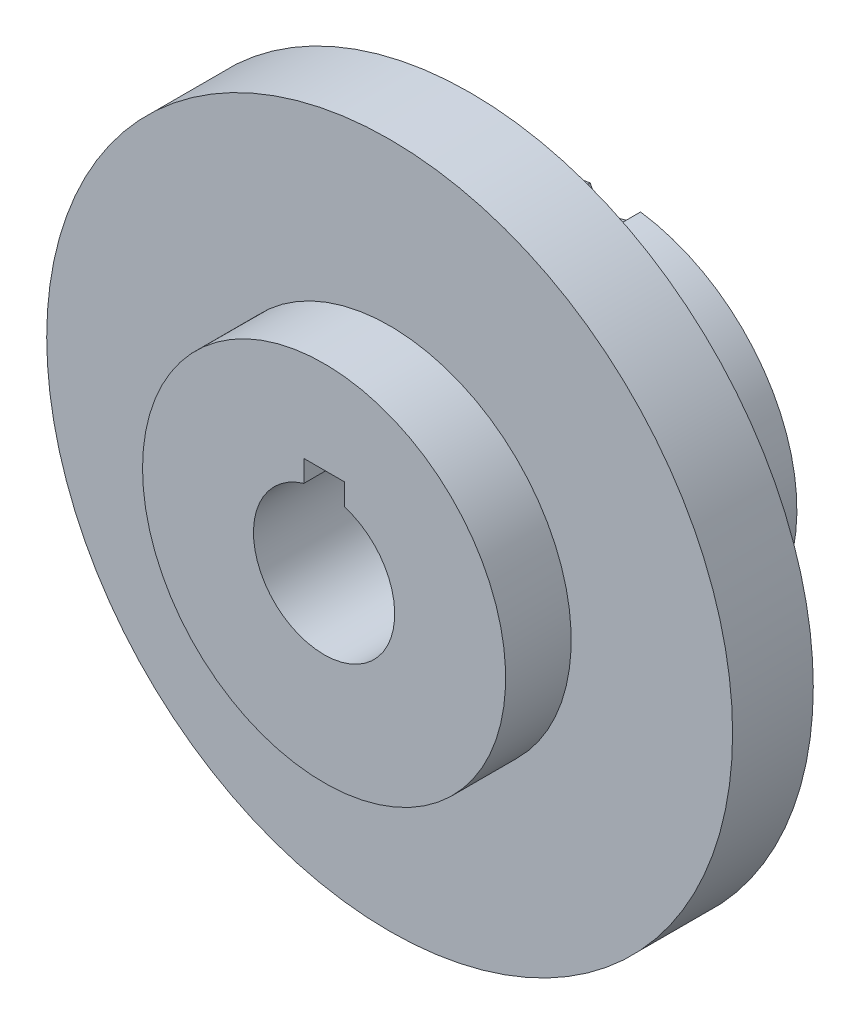
SolidWorks part; units mm, degrees
ref_plane "Спереди" through (0, 0, 0) normal (0, 0, 1) x (1, 0, 0)
ref_plane "Сверху" through (0, 0, 0) normal (0, 1, 0) x (1, 0, 0)
ref_plane "Справа" through (0, 0, 0) normal (1, 0, 0) x (0, 0, -1)
sketch "Эскиз1" plane through (0, 0, 0) normal (0, 0, 1) x (1, 0, 0)
  line L1 (-2, 8.85) -> (2, 8.85)
  line L2 (-2, 8.85) -> (-2, 6.7082)
  line L4 (2, 8.85) -> (2, 6.7082)
  arc A0 (-2, 6.7082) -> (2, 6.7082) centre (0, 0) ccw
  arc A1 (-2.5, 17.8255) -> (-16.6874, -6.7477) centre (0, 0) ccw
  arc A2 (-2.5, 17.8255) -> (2.5, 17.8255) centre (0, 18.9352) ccw
  arc A3 (-16.6874, -6.7477) -> (-14.1874, -11.0778) centre (-16.3984, -9.4676) cw
  arc A4 (14.1874, -11.0778) -> (16.6874, -6.7477) centre (16.3984, -9.4676) cw
  arc A5 (-14.1874, -11.0778) -> (14.1874, -11.0778) centre (0, 0) ccw
  arc A6 (16.6874, -6.7477) -> (2.5, 17.8255) centre (0, 0) ccw
  dimension "D1" = 14
  dimension "D2" = 36
  dimension "D4" = 2.7352
  dimension "D5" = 2.7352
  dimension "D6" = 2.7352
  dimension "D18" = 18
  dimension "D3" = 2
  dimension "D7" = 2
  dimension "D8" = 2.5
  dimension "D9" = 14.1874
  dimension "D10" = 16.3984
  dimension "D11" = 2.5
  dimension "D12" = 14.1874
  dimension "D13" = 16.3984
  dimension "D14" = 8.85
  dimension "D15" = 8.85
  dimension "D16" = 2
  dimension "D17" = 2
extrude "Вытянуть1" add sketch "Эскиз1" along normal up to surface (14.3746 mm away) from offset 6 offset against normal yes
sketch "Эскиз3" plane through (0, 0, 8.3746) normal (0, 0, 1) x (1, 0, 0)
  line L0 (-2, 8.85) -> (-2, 6.7082)
  line L1 (-2, 8.85) -> (2, 8.85)
  line L2 (2, 8.85) -> (2, 6.7082)
  circle A0 centre (0, 0) radius 34
  arc A1 (-2, 6.7082) -> (2, 6.7082) centre (0, 0) ccw
  dimension "D1" = 68
extrude "Вытянуть2" add sketch "Эскиз3" along normal blind 8
sketch "Эскиз5" plane through (0, 0, 16.3746) normal (0, 0, 1) x (1, 0, 0)
  line L0 (-2, 6.7082) -> (-2, 8.85)
  line L1 (-2, 8.85) -> (2, 8.85)
  line L2 (2, 8.85) -> (2, 6.7082)
  arc A0 (-2, 6.7082) -> (2, 6.7082) centre (0, 0) ccw
  circle A1 centre (0, 0) radius 18
  dimension "D1" = 36
extrude "Вытянуть3" add sketch "Эскиз5" along normal blind 6.5
